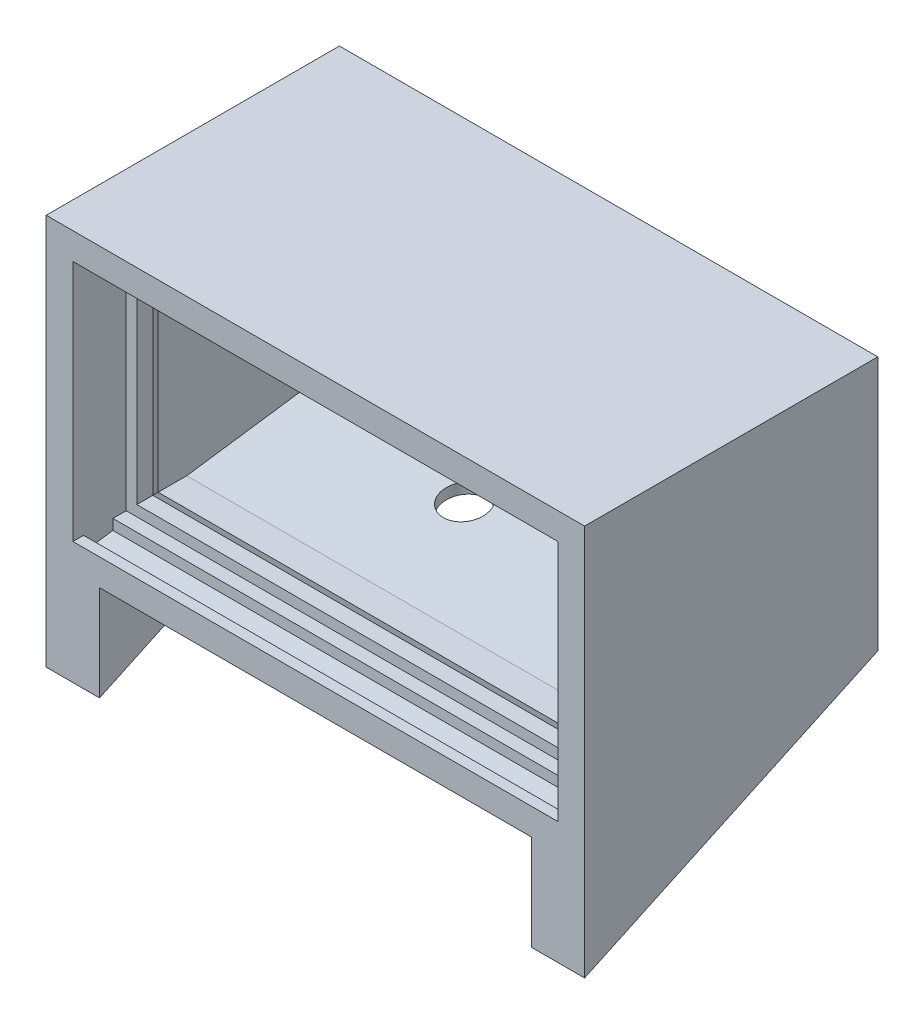
SolidWorks part; units mm, degrees
ref_plane "前视基准面" through (0, 0, 0) normal (0, 0, 1) x (1, 0, 0)
ref_plane "上视基准面" through (0, 0, 0) normal (0, 1, 0) x (1, 0, 0)
ref_plane "右视基准面" through (0, 0, 0) normal (1, 0, 0) x (0, 0, -1)
sketch "草图1" plane through (0, 0, 0) normal (0, 0, 1) x (1, 0, 0)
  line L0 (-50.5, 27.75) -> (50.5, 27.75)
  line L1 (-45.5, -22.75) -> (45.5, -22.75)
  line L2 (-45.5, -22.75) -> (-45.5, 22.75)
  line L3 (-45.5, 22.75) -> (45.5, 22.75)
  line L4 (45.5, -22.75) -> (45.5, 22.75)
  line L5 (0, 22.75) -> (0, -22.75) construction
  line L6 (-45.5, 0) -> (45.5, 0) construction
  line L7 (50.5, -27.75) -> (50.5, 27.75)
  line L8 (-50.5, -27.75) -> (50.5, -27.75)
  line L9 (-50.5, -27.75) -> (-50.5, 27.75)
  point P0 (0, 0)
  dimension "D1" = 91
  dimension "D2" = 45.5
  dimension "D3" = 5
extrude "凸台-拉伸1" add sketch "草图1" along normal blind 50
sketch "草图2" plane through (0, 0, 0) normal (0, 0, 1) x (1, 0, 0)
  line L0 (50.5, 27.75) -> (-50.5, 27.75) construction
  line L1 (-50.5, -27.75) -> (50.5, -27.75)
  line L2 (-50.5, -27.75) -> (-50.5, 27.75)
  line L3 (-50.5, 27.75) -> (50.5, 27.75)
  line L4 (50.5, -27.75) -> (50.5, 27.75)
  line L5 (50.5, -27.75) -> (50.5, 27.75) construction
extrude "凸台-拉伸2" add sketch "草图2" against normal blind 5
sketch "草图4" plane through (0, 22.75, 0) normal (0, -1, 0) x (1, 0, 0)
  line L0 (-50.5, 50) -> (-50.5, -5) construction
  line L1 (-50.5, 37) -> (50.5, 37)
  line L2 (-50.5, 37) -> (-50.5, 40)
  line L3 (-50.5, 40) -> (50.5, 40)
  line L4 (50.5, 37) -> (50.5, 40)
  line L5 (50.5, 50) -> (50.5, -5) construction
  line L7 (-50.5, 50) -> (50.5, 50) construction
  dimension "D1" = 10
  dimension "D2" = 3
extrude "凸台-拉伸3" add sketch "草图4" along normal blind 2
sketch "草图7" plane through (0, -22.75, 0) normal (0, 1, 0) x (1, 0, 0)
  line L0 (45.5, -50) -> (45.5, 0) construction
  line L1 (-45.5, -48) -> (45.5, -48)
  line L2 (-45.5, -48) -> (-45.5, -42.5)
  line L3 (-45.5, -42.5) -> (45.5, -42.5)
  line L4 (45.5, -48) -> (45.5, -42.5)
  line L5 (-45.5, -50) -> (45.5, -50) construction
  dimension "D1" = 5.5
  dimension "D2" = 2
  dimension "D3" = 91
extrude "切除-拉伸1" cut sketch "草图7" against normal blind 3
sketch "草图9" plane through (0, 0, 0) normal (0, 0, 1) x (1, 0, 0)
  line L0 (45.5, 22.75) -> (-45.5, 22.75) construction
  line L1 (-19.5, 22.75) -> (20.5, 22.75)
  line L2 (-19.5, 22.75) -> (-19.5, 13.75)
  line L3 (-19.5, 13.75) -> (20.5, 13.75)
  line L4 (20.5, 22.75) -> (20.5, 13.75)
  line L5 (-50.5, 27.75) -> (-50.5, -27.75) construction
  dimension "D1" = 40
  dimension "D2" = 9
  dimension "D3" = 31
extrude "切除-拉伸2" cut sketch "草图9" against normal blind 3
sketch "草图10" plane through (0, 0, -5) normal (0, 0, -1) x (-1, 0, 0)
  line L0 (-4.5, 16.25) -> (4.5, 16.25) construction
  line L1 (-4.5, 18.75) -> (4.5, 18.75)
  line L2 (-4.5, 13.75) -> (4.5, 13.75)
  line L3 (19.5, 13.75) -> (-20.5, 13.75) construction
  arc A0 (-4.5, 18.75) -> (-4.5, 13.75) centre (-4.5, 16.25) ccw
  arc A1 (4.5, 13.75) -> (4.5, 18.75) centre (4.5, 16.25) ccw
  point P2 (0, 16.25)
  dimension "D3" = 2.5
  dimension "D1" = 9
extrude "切除-拉伸3" cut sketch "草图10" against normal blind 10
sketch "草图11" plane through (50.5, 0, 0) normal (1, 0, 0) x (0, 0, -1)
  line L0 (-50, -27.75) -> (5, -20.0203)
  line L1 (5, -27.75) -> (5, 27.75) construction
  line L2 (5, -20.0203) -> (5, -27.75)
  line L3 (5, -27.75) -> (-50, -27.75)
  dimension "D1" = 8
extrude "切除-拉伸4" cut sketch "草图11" against normal blind 106
sketch "草图12" plane through (50.5, 0, 0) normal (1, 0, 0) x (0, 0, -1)
  line L0 (5, -20.0203) -> (5, -18.0203)
  line L1 (5, -20.0203) -> (5, 27.75) construction
  line L2 (5, -18.0203) -> (-50, -25.75)
  line L3 (-50, -27.75) -> (-50, 27.75) construction
  line L4 (-50, -25.75) -> (-50, -27.75)
  line L5 (-50, -27.75) -> (5, -20.0203)
  dimension "D1" = 2
extrude "凸台-拉伸4" add sketch "草图12" against normal blind 100
sketch "草图13" plane through (0, 0, 0) normal (0, 1, 0) x (1, 0, 0)
  line L0 (50.5, 5) -> (-50.5, 5) construction
  circle A0 centre (-12.5, -9.5) radius 4
  circle A1 centre (12.55, -9.5) radius 4
  dimension "D1" = 8
  dimension "D2" = 8
  dimension "D3" = 12.5
  dimension "D4" = 25.05
  dimension "D5" = 14.5
extrude "切除-拉伸5" cut sketch "草图13" against normal blind 137
sketch "草图14" plane through (0, 22.75, 0) normal (0, -1, 0) x (1, 0, 0)
  circle A0 centre (-12.5, 9.5) radius 3
  circle A1 centre (12.55, 9.5) radius 3
  circle A2 centre (-12.5, 9.5) radius 1.5
  circle A3 centre (12.55, 9.5) radius 1.5
  dimension "D1" = 6
  dimension "D2" = 6
  dimension "D3" = 3
  dimension "D4" = 3
extrude "凸台-拉伸5" add sketch "草图14" along normal blind 3
extrude "切除-拉伸6" cut sketch "草图14<3>" against normal blind 2 contours A2 | A3 region at (-12.5, 22.75, 9.5) region at (12.55, 22.75, 9.5)
sketch "草图14<3>" plane through (0, 22.75, 0) normal (0, -1, 0) x (1, 0, 0) same geometry as "草图14"
sketch "草图15" plane through (0, 0, 40) normal (0, 0, 1) x (1, 0, 0)
  line L0 (-45.5, -22.75) -> (45.5, -22.75) construction
  line L1 (-45.5, 20.75) -> (-43.5, 20.75)
  line L2 (-45.5, 20.75) -> (-45.5, -22.75)
  line L3 (-45.5, -22.75) -> (-43.5, -22.75)
  line L4 (-43.5, 20.75) -> (-43.5, -20.75)
  line L6 (45.5, 20.75) -> (43.5, 20.75)
  line L7 (45.5, 20.75) -> (45.5, -22.75)
  line L8 (45.5, -22.75) -> (43.3125, -22.75)
  line L9 (43.5, 20.75) -> (43.5, -20.75)
  line L10 (43.3125, -22.75) -> (-43.5, -22.75)
  line L12 (43.5, -20.75) -> (-43.5, -20.75)
  dimension "D1" = 2
  dimension "D2" = 2
  dimension "D3" = 2
extrude "凸台-拉伸6" add sketch "草图15" against normal blind 3
sketch "草图17" plane through (50.5, 0, 0) normal (1, 0, 0) x (0, 0, -1)
  line L0 (-50, -27.75) -> (-50, -45.6672)
  line L1 (-50, -45.6672) -> (5, -20.0203)
  line L2 (5, -20.0203) -> (-50, -27.75)
  dimension "D1" = 17
extrude "凸台-拉伸7" add sketch "草图17" against normal blind 10 contours L1 L2 L0
mirror "镜向1" about plane through (0, 0, 0) normal (1, 0, 0) of "凸台-拉伸7"
sketch "草图21" plane through (0, 22.75, 0) normal (0, -1, 0) x (1, 0, 0)
  line L0 (-45.5, 34) -> (-45.5, 37)
  line L1 (-45.5, 37) -> (-45.5, 0) construction
  line L2 (-45.5, 37) -> (-43.5, 37)
  line L3 (-43.5, 37) -> (-45.5, 34)
  line L4 (-43.5, 37) -> (43.5, 37) construction
  dimension "D1" = 3
  dimension "D2" = 2
extrude "凸台-拉伸9" add sketch "草图21" along normal up to next
mirror "镜向2" about plane through (0, 0, 0) normal (1, 0, 0) of "凸台-拉伸9"
sketch "草图18" plane through (0, 0, -3) normal (0, 0, 1) x (1, 0, 0)
  line L0 (45.5, 22.75) -> (-45.5, 22.75) construction
  line L1 (-14, 19.75) -> (-11, 19.75)
  line L2 (-14, 19.75) -> (-14, 22.75)
  line L3 (-14, 22.75) -> (-11, 22.75)
  line L4 (-11, 19.75) -> (-11, 22.75)
  line L6 (11.05, 19.75) -> (14.05, 19.75)
  line L7 (11.05, 19.75) -> (11.05, 22.75)
  line L8 (11.05, 22.75) -> (14.05, 22.75)
  line L9 (14.05, 19.75) -> (14.05, 22.75)
  dimension "D1" = 3
  dimension "D2" = 3
extrude "凸台-拉伸8" add sketch "草图18" along normal up to next
sketch "草图19" plane through (0, 0, 42.5) normal (0, 0, 1) x (1, 0, 0)
  line L0 (-45.5, -24.6959) -> (45.5, -24.6959) construction
  line L1 (45.5, -22.75) -> (40.5, -22.75)
  line L2 (45.5, -22.75) -> (45.5, -24.6959)
  line L3 (45.5, -24.6959) -> (40.5, -24.6959)
  line L4 (40.5, -22.75) -> (40.5, -24.6959)
  dimension "D1" = 5
extrude "切除-拉伸7" cut sketch "草图19" along direction (0, 0, -1) on the side against the normal blind 13
sketch "草图23" plane through (45.5, 0, 0) normal (-1, 0, 0) x (0, 0, 1)
  line L0 (34, 22.75) -> (37, 22.75)
  line L1 (34, 22.75) -> (0, 22.75) construction
  line L2 (37, 22.75) -> (37, 20.75)
  line L3 (37, 20.75) -> (34, 22.75)
  line L4 (37, 20.75) -> (37, -20.75) construction
  dimension "D1" = 3
  dimension "D2" = 2
extrude "凸台-拉伸10" add sketch "草图23" along normal up to surface (91 mm away) up to face at (-45.5, -3.7446, 19.3308)
sketch "草图24" plane through (-45.5, 0, 0) normal (1, 0, 0) x (0, 0, -1)
  line L0 (-34, -22.75) -> (-37, -22.75)
  line L1 (-34, -22.75) -> (-28.6539, -22.75) construction
  line L2 (-37, -22.75) -> (-37, -20.75)
  line L3 (-37, -20.75) -> (-34, -22.75)
  line L4 (-37, -20.75) -> (-37, 20.75) construction
  dimension "D1" = 3
  dimension "D2" = 2
extrude "凸台-拉伸11" add sketch "草图24" along normal up to surface (86 mm away) up to face at (40.5, -23.3986, 36.8333)
